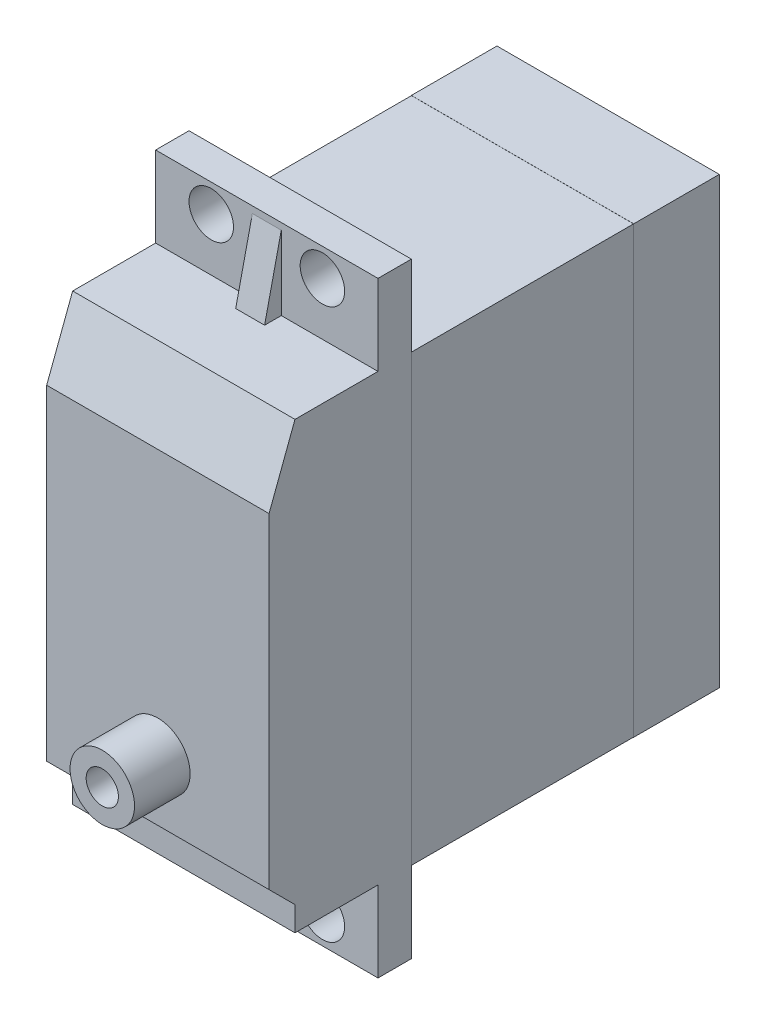
SolidWorks part; units mm, degrees
ref_plane "Front Plane" through (0, 0, 0) normal (1, 0, 0) x (0, 1, 0)
ref_plane "Top Plane" through (0, 0, 0) normal (0, 0, 1) x (0, 1, 0)
ref_plane "Right Plane" through (0, 0, 0) normal (0, 1, 0) x (-1, 0, 0)
sketch "Sketch1" plane through (0, 0, 0) normal (0, 0, 1) x (0, 1, 0)
  line L1 (-20, 10) -> (20, 10)
  line L2 (-20, 10) -> (-20, -10)
  line L3 (-20, -10) -> (20, -10)
  line L4 (20, 10) -> (20, -10)
  line L5 (-20, 10) -> (20, -10) construction
  line L6 (-20, -10) -> (20, 10) construction
  point P0 (0, 0)
  dimension "D1" = 20
  dimension "D2" = 40
extrude "Boss-Extrude1" add sketch "Sketch1" along normal blind 40.5
sketch "Sketch2" plane through (10, 0, 0) normal (1, 0, 0) x (0, 1, 0)
  line L0 (-20, 40.5) -> (-20, 0) construction
  line L1 (-20, 30.7) -> (-27.25, 30.7)
  line L2 (-20, 30.7) -> (-20, 27.7)
  line L3 (-20, 27.7) -> (-27.25, 27.7)
  line L4 (-27.25, 30.7) -> (-27.25, 27.7)
  line L5 (20, 40.5) -> (20, 0) construction
  line L6 (20, 30.7) -> (27.25, 30.7)
  line L7 (20, 30.7) -> (20, 27.7)
  line L8 (20, 27.7) -> (27.25, 27.7)
  line L9 (27.25, 30.7) -> (27.25, 27.7)
  line L10 (-20, 0) -> (20, 0) construction
  line L11 (20, 38.1665) -> (13.8263, 40.5)
  line L13 (13.8263, 40.5) -> (20, 40.5)
  line L14 (20, 40.5) -> (20, 38.1665)
  line L15 (-20, 38.1665) -> (-17.7986, 38.1665)
  line L16 (-17.7986, 38.1665) -> (-15.4651, 40.5)
  line L17 (-20, 40.5) -> (20, 40.5) construction
  line L18 (-15.4651, 40.5) -> (-20, 40.5)
  line L19 (-20, 40.5) -> (-20, 38.1665)
  point P20 (0, 0)
  point P26 (20, 37.9128)
  point P27 (-14.5027, 40.5)
  point P28 (20, 37.2356)
  point P29 (-15.4651, 40.5)
  point P30 (-20, 38.1665)
  point P31 (13.8263, 40.5)
  line M10 (20, 0) -> (20, 40.5)
  line M11 (20, 40.5) -> (-20, 40.5)
  line M12 (-20, 40.5) -> (-20, 0)
  dimension "D1" = 27.7
  dimension "D2" = 3
  dimension "D3" = 7.25
  dimension "D4" = 54.5
  dimension "D5" = 135
  dimension "D6" = 3.3
  dimension "D7" = 5.1
  dimension "D8" = 6.6
extrude "Boss-Extrude2" add sketch "Sketch2" against normal up to surface (20 mm away) up to face at (-10, 0, 20.25)
sketch "Sketch3" plane through (0, 0, 30.7) normal (0, 0, 1) x (1, 0, 0)
  line L0 (-5, 24.75) -> (5, -24.75) construction
  circle A0 centre (-5, 24.75) radius 2
  circle A1 centre (5, 24.75) radius 2
  circle A2 centre (-5, -24.75) radius 2
  circle A3 centre (5, -24.75) radius 2
  dimension "D1" = 10
  dimension "D3" = 4
  dimension "D2" = 49.5
extrude "Cut-Extrude1" cut sketch "Sketch3" against normal up to surface (3 mm away) up to face at (0, -23.625, 27.7)
sketch "Sketch4" plane through (0, 0, 40.5) normal (0, 0, 1) x (1, 0, 0)
  line L0 (-10, -20) -> (10, -20) construction
  circle A0 centre (0, -10) radius 2.9
  circle A3 centre (0, -10) radius 1.45
  dimension "D1" = 10
  dimension "D2" = 5.8
  dimension "D3" = 2.9
extrude "Boss-Extrude3" add sketch "Sketch4" along normal blind 5 contours A0 region at (-2.818, -10, 40.5)
extrude "Cut-Extrude2" cut sketch "Sketch2<2>" against normal up to surface (20 mm away) contours L15 L16 M11 M12 | L11 M10 M11 region at (10, 17.9421, 39.7222) region at (10, -18.2486, 39.468) up to face at (-10, 0, 26.2167)
sketch "Sketch2<2>" plane through (10, 0, 0) normal (1, 0, 0) x (0, 1, 0) same geometry as "Sketch2"
sketch "Sketch5" plane through (0, 0, 27.7) normal (0, 0, -1) x (1, 0, 0)
  line L1 (-10, 20) -> (10, 20)
  line L2 (-10, 20) -> (-10, -20)
  line L3 (-10, -20) -> (10, -20)
  line L4 (10, 20) -> (10, -20)
  line L16 (-9.99, -19.99) -> (9.99, -19.99)
  line L17 (9.99, -19.99) -> (9.99, 19.99)
  line L18 (9.99, 19.99) -> (-9.99, 19.99)
  line L19 (-9.99, 19.99) -> (-9.99, -19.99)
  line L20 (-9.99, -19.99) -> (9.99, -19.99)
  line L21 (9.99, -19.99) -> (9.99, 19.99)
  line L22 (9.99, 19.99) -> (-9.99, 19.99)
  line L23 (-9.99, 19.99) -> (-9.99, -19.99)
  dimension "D1" = 0.01
extrude "Cut-Extrude3" cut sketch "Sketch5" along normal blind 20
sketch "Sketch6" plane through (0, 0, 0) normal (1, 0, 0) x (0, 1, 0)
  line L0 (-26.65, 30.7) -> (-20, 32.2)
  line L1 (-20, 30.7) -> (-27.25, 30.7) construction
  line L2 (-20, 38.1665) -> (-20, 30.7) construction
  line L3 (-20, 32.2) -> (-20, 30.7)
  line L4 (-20, 30.7) -> (-26.65, 30.7)
  line L5 (20, 32.2) -> (26.65, 30.7)
  line L6 (20, 38.1665) -> (20, 30.7) construction
  line L8 (20, 30.7) -> (20, 32.2)
  line L9 (26.65, 30.7) -> (20, 30.7)
  line L10 (-27.25, 30.7) -> (-27.25, 27.7) construction
  dimension "D1" = 0.6
  dimension "D2" = 1.5
extrude "Boss-Extrude5" add sketch "Sketch6" along normal blind 1.3 and the other way blind 1.3
